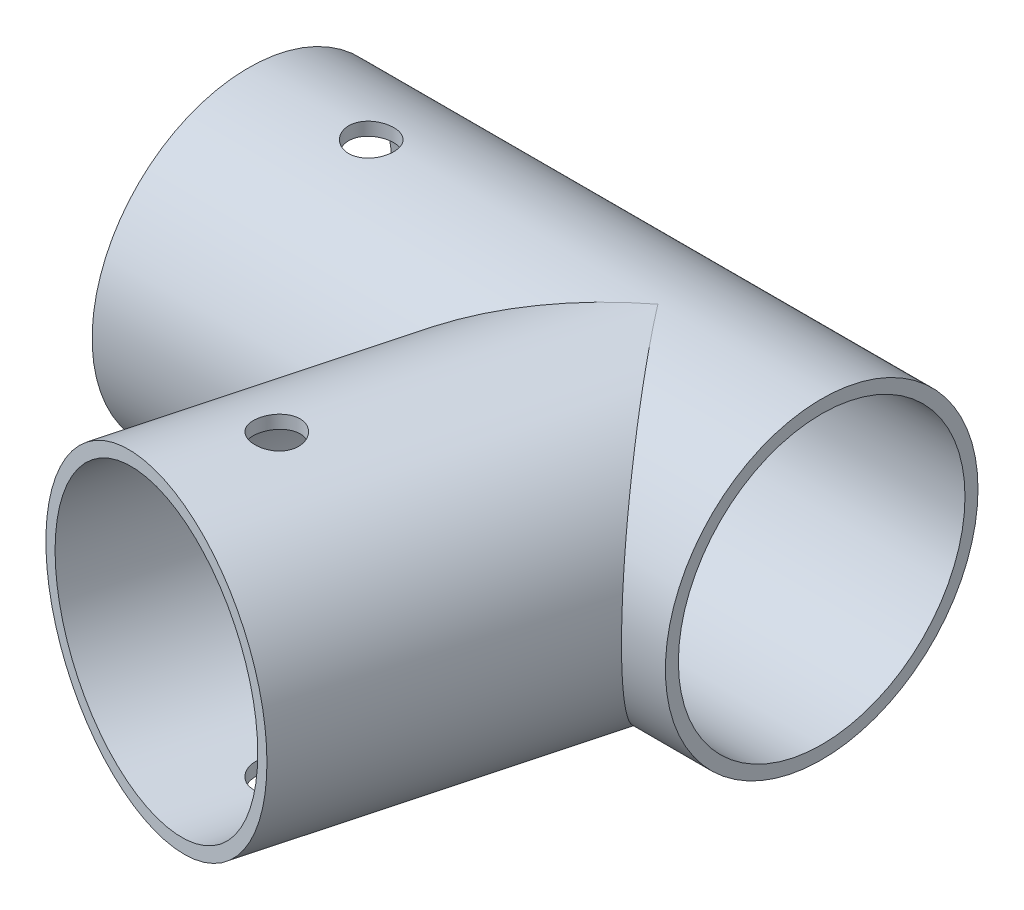
SolidWorks part; units mm, degrees
material "1060 Alloy"
ref_plane "Front Plane" through (0, 0, 0) normal (0, 0, 1) x (1, 0, 0)
ref_plane "Top Plane" through (0, 0, 0) normal (0, 1, 0) x (1, 0, 0)
ref_plane "Right Plane" through (0, 0, 0) normal (1, 0, 0) x (0, 0, -1)
sketch "Sketch1" plane through (0, 0, 0) normal (0, 1, 0) x (1, 0, 0)
  line L0 (0, 0) -> (100, 0) construction
  line L1 (50, 0) -> (37.059, -48.2963) construction
  dimension "D1" = 100
  dimension "D2" = 50
  dimension "D3" = 75
ref_plane "Plane1" through (0, 0, 0) normal (1, 0, 0) x (0, 0, -1)
sketch "Sketch2" plane through (0, 0, 0) normal (1, 0, 0) x (0, 0, -1)
  circle A0 centre (0, 0) radius 19.0875
  dimension "D1" = 38.175
extrude "Boss-Extrude1" add sketch "Sketch2" along normal up to vertex (100 mm away) up to point (100, 0, 0)
ref_plane "Plane2" through (37.059, 0, 48.2963) normal (-0.2588, 0, 0.9659) x (0.9659, 0, 0.2588)
sketch "Sketch3" plane through (37.059, 0, 48.2963) normal (-0.2588, 0, 0.9659) x (0.9659, 0, 0.2588)
  line L0 (-48.2963, 0) -> (48.2963, 0) construction
  circle A0 centre (0, 0) radius 19.0875
  dimension "D1" = 38.175
extrude "Boss-Extrude2" add sketch "Sketch3" against normal up to surface (35.3536 mm away) up to face at (100, 0, -19.0875)
shell "Shell1" thickness 1.5875 removed face at (100, 0, -19.0875) removed face at (0, 0, -19.0875) removed face at (55.4962, 0, 53.2365)
sketch "Sketch4" plane through (0, 0, 0) normal (0, 1, 0) x (1, 0, 0)
  line L0 (37.059, -48.2963) -> (40.1649, -36.7052) construction
  line L1 (18.6219, -43.3561) -> (55.4962, -53.2365) construction
  line L2 (0, 0) -> (15, 0) construction
  dimension "D1" = 90
  dimension "D2" = 12
  dimension "D3" = 15
hole_wizard "M5 Clearance Hole1" positions "Sketch5" profile "Sketch6" hole size "M5" standard "AS" end condition through all
sketch "Sketch5" plane through (0, 0, 0) normal (0, 1, 0) x (1, 0, 0)
  point P0 (15, 0)
  point P3 (40.1649, -36.7052)
sketch "Sketch6" plane through (15, 0, 0) normal (1, 0, 0) x (0, 0, -1)
  line L0 (0, 0) -> (0, 19.0875)
  line L1 (0, 19.0875) -> (2.75, 19.0875)
  line L2 (2.75, 19.0875) -> (2.75, 0)
  line L5 (2.75, 0) -> (0, 0)
  line L11 (0, -6.35) -> (0, 107.95) construction
  dimension "Thru Hole Dia." = 5.5
  dimension "Thru Hole Depth" = 19.0875
mirror "Mirror1" about plane through (0, 0, 0) normal (0, 1, 0) of "M5 Clearance Hole1"
sketch "Sketch7" plane through (100, 0, 0) normal (1, 0, 0) x (0, 0, -1)
  circle A0 centre (0, 0) radius 19.0875
  circle A1 centre (0, 0) radius 17.5
  circle A2 centre (0, 0) radius 19.0875 construction
  circle A3 centre (0, 0) radius 17.5 construction
extrude "Cut-Extrude1" cut sketch "Sketch7" against normal blind 30
equation "\"frontTubeLength\"= 1200mm"
equation "\"outDiameter\"= 35mm"
equation "\"keelOutDiameter\"= 1in"
equation "\"D1@Sketch2\"=\"outDiameter\"+0.125in"
equation "\"D1@Sketch3\"=\"outDiameter\"+0.125in"
equation "\"bottomTubeLength\"= \"frontTubeLength\"*0.9"
equation "\"frontShaftDiameter\"= 20mm"
